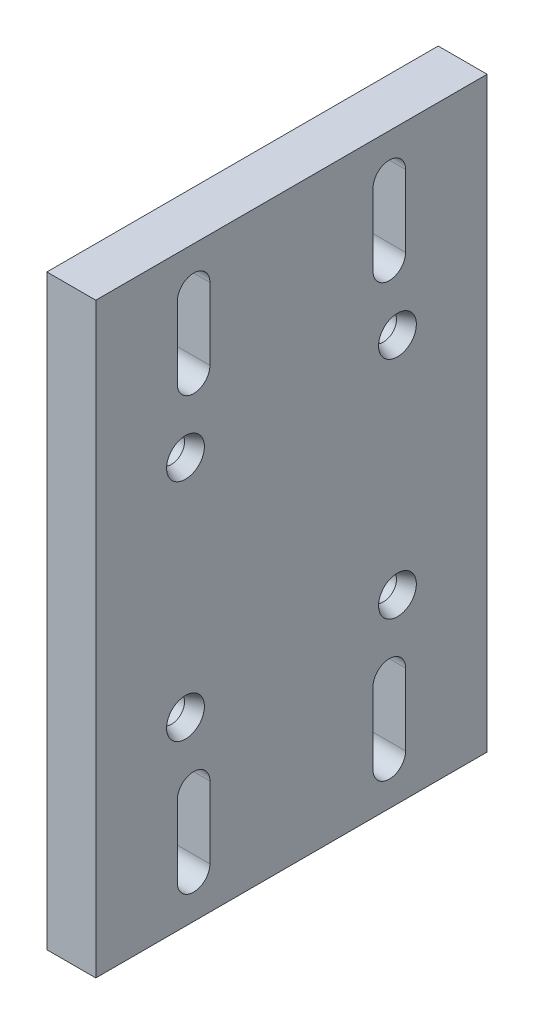
SolidWorks part; units mm, degrees
ref_plane "Front Plane" through (0, 0, 0) normal (0, 0, 1) x (1, 0, 0)
ref_plane "Top Plane" through (0, 0, 0) normal (0, 1, 0) x (1, 0, 0)
ref_plane "Right Plane" through (0, 0, 0) normal (1, 0, 0) x (0, 0, -1)
sketch "Sketch1" plane through (0, 0, 0) normal (1, 0, 0) x (0, 0, -1)
  line L1 (-38.1, -57.15) -> (38.1, -57.15)
  line L2 (-38.1, -57.15) -> (-38.1, 57.15)
  line L3 (-38.1, 57.15) -> (38.1, 57.15)
  line L4 (38.1, -57.15) -> (38.1, 57.15)
  line L5 (-38.1, -57.15) -> (38.1, 57.15) construction
  line L6 (-38.1, 57.15) -> (38.1, -57.15) construction
  point P0 (0, 0)
  point P5 (0, 0)
  dimension "D1" = 76.2
  dimension "D2" = 114.3
extrude "Boss-Extrude1" add sketch "Sketch1" along normal blind 9.525
hole_wizard "1/4-20 Tapped Hole1" positions "Sketch2" profile "Sketch3" tap size "1/4-20" standard "ANSI Inch" end condition through all
sketch "Sketch2" plane through (9.525, 0, 0) normal (1, 0, 0) x (0, 0, -1)
  line L1 (-20.6375, -21.9075) -> (20.6375, -21.9075) construction
  line L2 (-20.6375, -21.9075) -> (-20.6375, 21.9075) construction
  line L3 (-20.6375, 21.9075) -> (20.6375, 21.9075) construction
  line L4 (20.6375, -21.9075) -> (20.6375, 21.9075) construction
  line L5 (-20.6375, -21.9075) -> (20.6375, 21.9075) construction
  line L6 (-20.6375, 21.9075) -> (20.6375, -21.9075) construction
  point P0 (-20.6375, 21.9075)
  point P58 (20.6375, 21.9075)
  point P61 (20.6375, -21.9075)
  point P64 (-20.6375, -21.9075)
  point P81 (0, 0)
  point P82 (0, 0)
  dimension "D1" = 43.815
  dimension "D2" = 41.275
sketch "Sketch3" plane through (9.525, 21.9075, 20.6375) normal (0, 1, 0) x (0, 0, -1)
  line L0 (0, 0) -> (0, 9.525)
  line L1 (0, 9.525) -> (2.5527, 9.525)
  line L2 (2.5527, 9.525) -> (2.5527, 2.7288)
  line L3 (2.5527, 2.7288) -> (3.683, 0)
  line L5 (3.683, 0) -> (0, 0)
  line L6 (-2.5527, 2.7288) -> (-3.683, 0) construction
  line L11 (0, -6.35) -> (0, 107.95) construction
  dimension "Thru Tap Drill Dia." = 5.1054
  dimension "Thru Tap Drill Depth" = 9.525
  dimension "Near C'Sink Dia." = 7.366
  dimension "Near C'Sink Angle" = 45
cosmetic thread "Hole Thread1" parameters "D2"=6.35
cosmetic thread "Hole Thread2" parameters "D2"=6.35
cosmetic thread "Hole Thread3" parameters "D2"=6.35
cosmetic thread "Hole Thread4" parameters "D2"=6.35
sketch "Sketch4" plane through (9.525, 0, 0) normal (1, 0, 0) x (0, 0, -1)
  line L5 (19.05, 29.972) -> (19.05, 57.15) construction
  line L6 (38.1, 57.15) -> (-38.1, 57.15) construction
  line L7 (0, -57.15) -> (0, 57.15) construction
  line L8 (-29.972, 29.972) -> (29.972, 29.972) construction
  line L9 (-29.972, 29.972) -> (-29.972, -29.972) construction
  line L10 (-29.972, -29.972) -> (29.972, -29.972) construction
  line L11 (29.972, 29.972) -> (29.972, -29.972) construction
  line L12 (-29.972, 29.972) -> (29.972, -29.972) construction
  line L13 (-29.972, -29.972) -> (29.972, 29.972) construction
  line L14 (-38.1, -57.15) -> (38.1, -57.15) construction
  line L15 (-38.1, 0) -> (38.1, 0) construction
  line L16 (15.875, 49.022) -> (22.225, 49.022) construction
  line L17 (15.875, 49.022) -> (15.875, 35.052)
  line L18 (15.875, 35.052) -> (22.225, 35.052) construction
  line L19 (22.225, 49.022) -> (22.225, 35.052)
  line L20 (15.875, 49.022) -> (22.225, 35.052) construction
  line L21 (15.875, 35.052) -> (22.225, 49.022) construction
  line L22 (-38.1, 57.15) -> (-38.1, -57.15) construction
  line L23 (38.1, -57.15) -> (38.1, 57.15) construction
  line L24 (-15.875, 35.052) -> (-22.225, 49.022) construction
  line L25 (-15.875, 49.022) -> (-22.225, 35.052) construction
  line L26 (-15.875, 35.052) -> (-22.225, 35.052) construction
  line L27 (-15.875, 49.022) -> (-22.225, 49.022) construction
  line L28 (-22.225, 49.022) -> (-22.225, 35.052)
  line L29 (-15.875, 49.022) -> (-15.875, 35.052)
  line L30 (-15.875, -49.022) -> (-22.225, -49.022) construction
  line L31 (-15.875, -35.052) -> (-22.225, -35.052) construction
  line L32 (-15.875, -49.022) -> (-22.225, -35.052) construction
  line L33 (-15.875, -35.052) -> (-22.225, -49.022) construction
  line L34 (15.875, -35.052) -> (22.225, -49.022) construction
  line L35 (15.875, -49.022) -> (22.225, -35.052) construction
  line L36 (15.875, -35.052) -> (22.225, -35.052) construction
  line L37 (15.875, -49.022) -> (22.225, -49.022) construction
  line L38 (-15.875, -49.022) -> (-15.875, -35.052)
  line L39 (-22.225, -49.022) -> (-22.225, -35.052)
  line L40 (22.225, -49.022) -> (22.225, -35.052)
  line L41 (15.875, -49.022) -> (15.875, -35.052)
  line L42 (11.0908, 31.877) -> (29.972, 31.877) construction
  arc A0 (15.875, 49.022) -> (22.225, 49.022) centre (19.05, 49.022) cw
  arc A1 (22.225, 35.052) -> (15.875, 35.052) centre (19.05, 35.052) cw
  arc A2 (-22.225, 35.052) -> (-15.875, 35.052) centre (-19.05, 35.052) ccw
  arc A3 (-15.875, 49.022) -> (-22.225, 49.022) centre (-19.05, 49.022) ccw
  arc A4 (-15.875, -49.022) -> (-22.225, -49.022) centre (-19.05, -49.022) cw
  arc A5 (-22.225, -35.052) -> (-15.875, -35.052) centre (-19.05, -35.052) cw
  arc A6 (22.225, -35.052) -> (15.875, -35.052) centre (19.05, -35.052) ccw
  arc A7 (15.875, -49.022) -> (22.225, -49.022) centre (19.05, -49.022) ccw
  point P7 (0, 0)
  point P13 (19.05, 42.037)
  point P33 (-19.05, 42.037)
  point P46 (-19.05, -42.037)
  point P47 (19.05, -42.037)
  point P48 (11.0908, 31.877)
  point P49 (29.972, 31.877)
  dimension "D4" = 19.05
  dimension "D1" = 13.97
  dimension "D2" = 59.944
  dimension "D3" = 6.35
  dimension "D5" = 1.905
extrude "Cut-Extrude1" cut sketch "Sketch4" against normal through all
ref_axis "Axis1" through (0, 0, 0) along (1, 0, 0)
